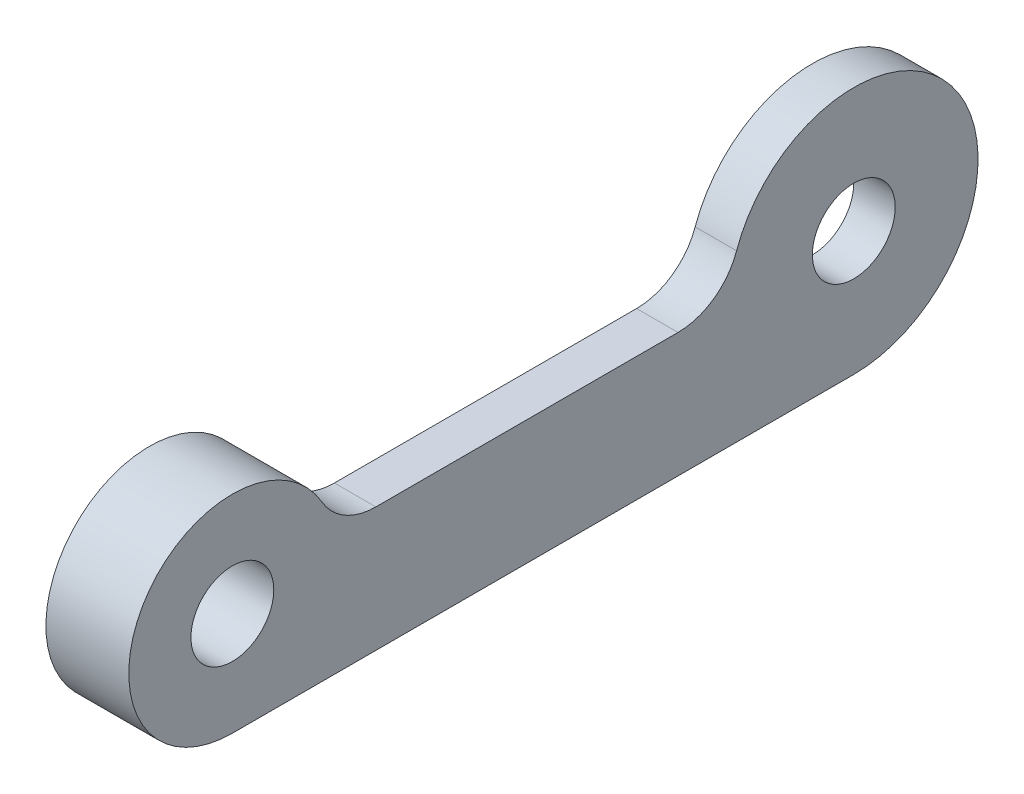
SolidWorks part; units mm, degrees
ref_plane "前视基准面" through (0, 0, 0) normal (0, 0, 1) x (1, 0, 0)
ref_plane "上视基准面" through (0, 0, 0) normal (0, 1, 0) x (1, 0, 0)
ref_plane "右视基准面" through (0, 0, 0) normal (1, 0, 0) x (0, 0, -1)
other "Configuration Table"
sketch "草图1" plane through (0, 0, 0) normal (1, 0, 0) x (0, 0, -1)
  line L1 (0, 0) -> (30, 0)
  line L2 (0, 0) -> (0, -6)
  line L3 (0, -6) -> (30, -6)
  line L4 (30, 0) -> (30, -6)
  circle A0 centre (0, -1) radius 5
  circle A1 centre (30, 0) radius 6
  circle A2 centre (0, -1) radius 2
  circle A3 centre (30, 0) radius 2
  dimension "D1" = 10
  dimension "D2" = 12
  dimension "D4" = 4
  dimension "D3" = 6
  dimension "D5" = 30
extrude "凸台-拉伸1" add sketch "草图1" along normal blind 2 contours A0 | L1 L4 L3 L2 | A1
extrude "凸台-拉伸3" add sketch "草图1<5>" against normal blind 2 contours A0
sketch "草图1<5>" plane through (0, 0, 0) normal (1, 0, 0) x (0, 0, -1) same geometry as "草图1"
extrude "切除-拉伸2" cut sketch "草图1<4>" along normal through all both and the other way through all contours L2 A2 | L2 A2 | L4 A3 L1 | L1 A3 L4 region at (0, -0.7694, 0.5991) region at (0, -1.3427, -0.8902) region at (0, 0.2829, -30.2829) region at (0, -0.8488, -29.1512)
sketch "草图1<4>" plane through (0, 0, 0) normal (1, 0, 0) x (0, 0, -1) same geometry as "草图1"
fillet "圆角1" radius 3 2 edges at (1, 0, -24) (1, 0, -4.899)
